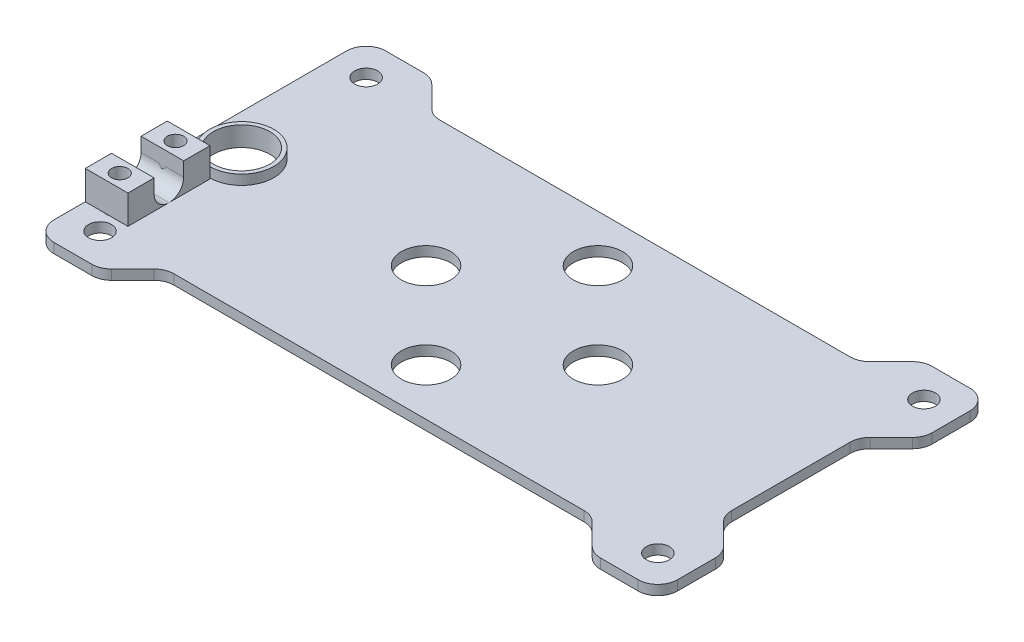
SolidWorks part; units mm, degrees
ref_plane "Front Plane" through (0, 0, 0) normal (0, 0, 1) x (1, 0, 0)
ref_plane "Top Plane" through (0, 0, 0) normal (0, 1, 0) x (1, 0, 0)
ref_plane "Right Plane" through (0, 0, 0) normal (1, 0, 0) x (0, 0, -1)
sketch "Sketch1" plane through (0, 0, 0) normal (0, 1, 0) x (1, 0, 0)
  line L0 (0, 25.275) -> (0, -25.275) construction
  line L1 (-47.5, 25.275) -> (47.5, 25.275)
  line L2 (-47.5, 25.275) -> (-47.5, -25.275)
  line L3 (-47.5, -25.275) -> (47.5, -25.275)
  line L4 (47.5, 25.275) -> (47.5, -25.275)
  line L5 (-47.5, 25.275) -> (47.5, -25.275) construction
  line L6 (-47.5, -25.275) -> (47.5, 25.275) construction
  line L7 (-47.5, 0) -> (47.5, 0) construction
  line L8 (-45.5, 0) -> (-45.5, 25.275) construction
  circle A0 centre (-42.5, 20.275) radius 1.75
  circle A1 centre (42.5, 20.275) radius 1.75
  circle A2 centre (42.5, -20.275) radius 1.75
  circle A3 centre (-42.5, -20.275) radius 1.75
  circle A4 centre (-13.1, 0) radius 3.75
  circle A5 centre (13.1, 0) radius 3.75
  circle A6 centre (0, 13.1) radius 3.75
  circle A7 centre (0, -13.1) radius 3.75
  circle A8 centre (-41.2, 0) radius 4.3
  point P0 (0, 0)
  dimension "D5" = 3.5
  dimension "D6" = 7.5
  dimension "D9" = 8.6
  dimension "D1" = 85
  dimension "D2" = 40.55
  dimension "D3" = 5
  dimension "D4" = 5
  dimension "D7" = 26.2
  dimension "D8" = 26.2
  dimension "D10" = 2
extrude "Boss-Extrude1" add sketch "Sketch1" along normal blind 1.5
sketch "Sketch2" plane through (0, 1.5, 0) normal (0, 1, 0) x (1, 0, 0)
  line L0 (-47.5, 25.275) -> (-47.5, -25.275) construction
  line L1 (47.5, 20.275) -> (-47.5, 20.275)
  line L2 (47.5, 20.275) -> (47.5, -20.275)
  line L3 (47.5, -20.275) -> (-47.5, -20.275)
  line L4 (-47.5, 20.275) -> (-47.5, -20.275)
  line L5 (47.5, 20.275) -> (-47.5, -20.275) construction
  line L6 (47.5, -20.275) -> (-47.5, 20.275) construction
  line L7 (-47.5, -25.275) -> (47.5, -25.275) construction
  line L8 (-42.5, 25.275) -> (42.5, 25.275)
  line L9 (-42.5, 25.275) -> (-42.5, -25.275)
  line L10 (-42.5, -25.275) -> (42.5, -25.275)
  line L11 (42.5, 25.275) -> (42.5, -25.275)
  line L12 (-42.5, 25.275) -> (42.5, -25.275) construction
  line L13 (-42.5, -25.275) -> (42.5, 25.275) construction
  line L14 (-37.5, 25.275) -> (-32.5, 20.275)
  line L15 (37.5, 25.275) -> (-37.5, 25.275)
  line L16 (37.5, 25.275) -> (37.5, -25.275)
  line L17 (37.5, -25.275) -> (-37.5, -25.275)
  line L18 (-37.5, 25.275) -> (-37.5, -25.275)
  line L19 (37.5, 25.275) -> (-37.5, -25.275) construction
  line L20 (37.5, -25.275) -> (-37.5, 25.275) construction
  line L21 (47.5, 15.275) -> (-47.5, 15.275)
  line L22 (47.5, 15.275) -> (47.5, -15.275)
  line L23 (47.5, -15.275) -> (-47.5, -15.275)
  line L24 (-47.5, 15.275) -> (-47.5, -15.275)
  line L25 (47.5, 15.275) -> (-47.5, -15.275) construction
  line L26 (47.5, -15.275) -> (-47.5, 15.275) construction
  line L27 (37.5, 25.275) -> (32.5, 20.275)
  line L28 (-47.5, 0) -> (47.5, 0) construction
  line L29 (37.5, -25.275) -> (32.5, -20.275)
  line L30 (-37.5, -25.275) -> (-32.5, -20.275)
  line L31 (-47.5, 15.275) -> (-42.5, 10.275)
  line L32 (-47.5, -15.275) -> (-42.5, -10.275)
  line L33 (0, 25.275) -> (0, -25.275) construction
  line L34 (47.5, 15.275) -> (42.5, 10.275)
  line L35 (47.5, -15.275) -> (42.5, -10.275)
  point P0 (0, 0)
  point P8 (0, 0)
  point P15 (0, 0)
  point P20 (0, 0)
  dimension "D1" = 5
  dimension "D2" = 5
  dimension "D3" = 10
  dimension "D4" = 10
  dimension "D5" = 45
  dimension "D6" = 45
  dimension "D7" = 45
  dimension "D8" = 45
  dimension "D9" = 45
  dimension "D10" = 45
extrude "Cut-Extrude1" cut sketch "Sketch2" against normal blind 1.5 contours L27 L8 L14 L1 | L30 L10 L29 L3 | L35 L2 L34 L11 region at (0, 1.5, -22.8345) region at (45.1631, 1.5, 0) region at (0, 1.5, 22.8345)
fillet "Fillet1" radius 3 16 edges at (37.5, 0.75, -25.275) (32.5, 0.75, -20.275) (-32.5, 0.75, -20.275) (-37.5, 0.75, -25.275) (47.5, 0.75, -15.275) (42.5, 0.75, -10.275) (42.5, 0.75, 10.275) (47.5, 0.75, 15.275) (37.5, 0.75, 25.275) (32.5, 0.75, 20.275) (-32.5, 0.75, 20.275) (-37.5, 0.75, 25.275) (-47.5, 0.75, -25.275) (47.5, 0.75, -25.275) (47.5, 0.75, 25.275) (-47.5, 0.75, 25.275)
sketch "Sketch3" plane through (0, 1.5, 0) normal (0, 1, 0) x (1, 0, 0)
  circle A0 centre (-41.2, 0) radius 4.3 construction
  circle A1 centre (-41.2, 0) radius 4.3
  circle A2 centre (-41.2, 0) radius 4.9
  dimension "D1" = 9.8
extrude "Boss-Extrude2" add sketch "Sketch3" along normal blind 1.5
sketch "Sketch5" plane through (0, 1.5, 0) normal (0, 1, 0) x (1, 0, 0)
  line L0 (-47.5, -11.275) -> (43.5, -11.275) construction
  line L1 (-47.5, 22.275) -> (-47.5, -22.275) construction
  line L2 (46.6213, -14.3963) -> (43.3787, -11.1537) construction
  line L3 (-44.5, -25.275) -> (-38.7426, -25.275) construction
  line L5 (-47.5, -9.025) -> (-41, -9.025)
  line L6 (-47.5, -9.025) -> (-47.5, -13.525)
  line L7 (-47.5, -13.525) -> (-41, -13.525)
  line L8 (-41, -9.025) -> (-41, -13.525)
  line L9 (-47.5, -9.025) -> (-41, -13.525) construction
  line L10 (-47.5, -13.525) -> (-41, -9.025) construction
  line L11 (-47.5, -9.025) -> (-41, -9.025)
  line L12 (-47.5, -9.025) -> (-47.5, -5.025)
  line L13 (-47.5, -5.025) -> (-41, -5.025)
  line L14 (-41, -9.025) -> (-41, -5.025)
  line L15 (-47.5, -13.525) -> (-41, -13.525)
  line L16 (-47.5, -13.525) -> (-47.5, -17.525)
  line L17 (-47.5, -17.525) -> (-41, -17.525)
  line L18 (-41, -13.525) -> (-41, -17.525)
  point P8 (-44.25, -11.275)
  line M11 (-47.5, 22.275) -> (-47.5, -22.275)
  dimension "D1" = 14
  dimension "D2" = 6.5
  dimension "D3" = 4.5
  dimension "D4" = 4
extrude "Boss-Extrude3" add sketch "Sketch5" along normal blind 4.4 contours L5 L14 L13 M11 | L18 L7 L17 M11 region at (-44.25, 1.5, 7.025) region at (-44.25, 1.5, 15.525)
sketch "Sketch6" plane through (0, 5.9, 0) normal (0, 1, 0) x (1, 0, 0)
  line L0 (-44.25, -5.025) -> (-44.25, -17.525) construction
  line L1 (-47.5, -5.025) -> (-41, -5.025) construction
  line L2 (-47.5, -17.525) -> (-41, -17.525) construction
  line L3 (-47.5, -7.025) -> (-41, -7.025) construction
  line L4 (-47.5, -5.025) -> (-47.5, -9.025) construction
  line L5 (-41, -9.025) -> (-41, -5.025) construction
  line L6 (-47.5, -15.525) -> (-41, -15.525) construction
  line L7 (-47.5, -13.525) -> (-47.5, -17.525) construction
  line L8 (-41, -13.525) -> (-41, -17.525) construction
  circle A0 centre (-44.25, -7.025) radius 1.25
  circle A1 centre (-44.25, -15.525) radius 1.25
  dimension "D1" = 2.5
extrude "Cut-Extrude2" cut sketch "Sketch6" against normal up to next
sketch "Sketch8" plane through (0, 0, 0) normal (0, -1, 0) x (1, 0, 0)
  circle A0 centre (-44.25, 15.525) radius 2.05
  circle A1 centre (-44.25, 7.025) radius 2.05
  dimension "D1" = 4.1
extrude "Cut-Extrude3" cut sketch "Sketch8" against normal blind 1.5
fillet "Fillet2" radius 2.25 4 edges at (-46.1, 1.5, 13.525) (-42.4, 1.5, 13.525) (-46.1, 1.5, 9.025) (-42.4, 1.5, 9.025)
equation "\"support-diameter\"=26.2"
equation "\"D7@Sketch1\"=\"support-diameter\""
equation "\"D8@Sketch1\"=\"support-diameter\""
